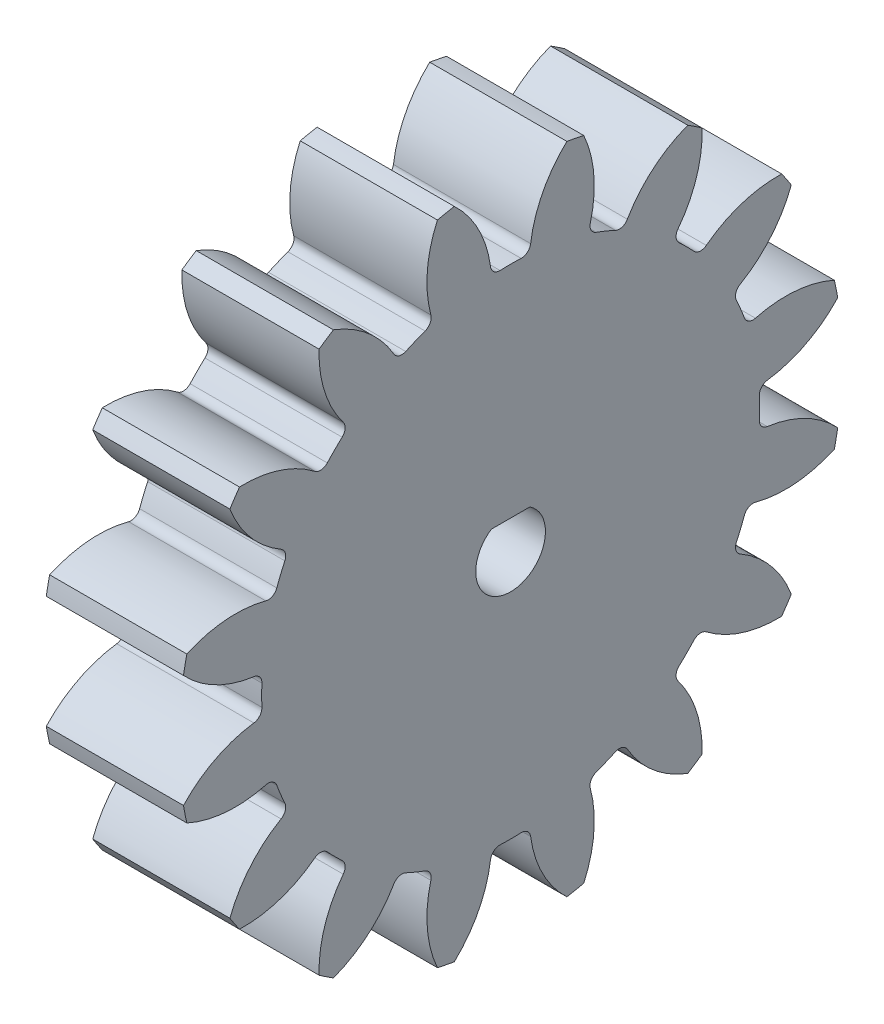
SolidWorks part; units mm, degrees
ref_plane "Plane1" through (0, 0, 0) normal (0, 0, 1) x (1, 0, 0)
ref_plane "Plane2" through (0, 0, 0) normal (0, 1, 0) x (1, 0, 0)
ref_plane "Plane3" through (0, 0, 0) normal (1, 0, 0) x (0, 0, -1)
sketch "HoldingSke" plane through (0, 0, 0) normal (0, 1, 0) x (1, 0, 0)
  line L0 (0, 0) -> (195.3284, -56.0095)
  line L1 (-15, 0) -> (100, 0) construction
  line L2 (0, 0) -> (-2.1039, 2.3779)
  line L3 (0, 0) -> (-11.863, 4.5341)
  line L4 (0, 0) -> (8.3015, 2.3804)
  line L5 (0, 0) -> (-47.5972, -17.7524)
  line L6 (0, 0) -> (-9.7909, -6.6059)
  line L7 (-2.1039, 2.3779) -> (8.8308, 51.9871)
  line L8 (-76.2, 54.61) -> (-75.184, 54.61)
  line L9 (-71.009, 38.7566) -> (-53.1078, 45.2721)
  line L10 (-76.2, 71.12) -> (104.1128, 71.12)
  line L11 (0, 0) -> (-11.811, 0)
  line L12 (-76.2, 101.6) -> (-76.0857, 101.6)
  line L13 (24.9733, 27.94) -> (52.9518, 28.4284)
  line L14 (24.9733, 27.94) -> (24.9746, 27.94)
  line L15 (24.9733, 27.94) -> (100.4006, 29.5858)
  circle A0 centre (0, 0) radius 0.3969
  circle A1 centre (0, 0) radius 21.43
  circle A2 centre (0, 0) radius 38.1
  circle A3 centre (0, 0) radius 0.3969
  dimension "MHD" = 42.86
  dimension "Hub_dia" = 76.2
  dimension "Bore" = 0.7937
  dimension "MBD" = 0.7937
  dimension "Num_teeth" = 16
  dimension "Pitch_radius" = 180.3128
  dimension "Pitch" = 203.2
  dimension "Width" = 11.811
  dimension "Overall_len" = 50.8
  dimension "Show_teeth" = 16
  dimension "Thickness" = 11.811
  dimension "OAL" = 50.8001
  dimension "T_dim" = 1.016
  dimension "Ap" = 20
  dimension "H" = 19.05
  dimension "Backlash" = 0.1143
  dimension "Addendum_fac" = 1
  dimension "Dedendum_fac" = 1.25
  dimension "Clearance_fac" = 0.25
  dimension "Dedendum_add" = 0.0013
sketch "BasProSke" plane through (0, 0, 0) normal (0, 1, 0) x (1, 0, 0)
  line L0 (-10, 0) -> (60, 0) construction
  line L1 (0, 0) -> (0, 28.575)
  line L2 (0, 0) -> (11.811, 0)
  line L3 (11.811, 0) -> (11.811, 28.575)
  line L4 (11.811, 28.575) -> (0, 28.575)
  dimension "Diameter" = 57.15
  dimension "Thickness" = 11.811
revolve "Base-Revolve" add sketch "BasProSke" angle 360 about L0
sketch "TooCutSke" plane through (0, 0, 0) normal (1, 0, 0) x (0, 0, -1)
  line L1 (0, 0) -> (0, 107) construction
  line L2 (0, 0) -> (-2.6895, 25.2572) construction
  line L3 (0, 0) -> (-9.8702, 49.6211) construction
  line L4 (-2.6895, 25.2572) -> (-4.9351, 24.8105) construction
  arc A0 (1.6538, 21.3661) -> (-1.6538, 21.3661) centre (0, 0) ccw
  arc A1 (4.8685, 28.183) -> (-4.8685, 28.183) centre (0, 0) ccw
  circle A2 centre (0, 0) radius 25.4 construction
  circle A3 centre (0, 0) radius 23.8682 construction
  arc A4 (-1.6538, 21.3661) -> (-4.8685, 28.183) centre (-11.7951, 20.7501) ccw
  arc A5 (4.8685, 28.183) -> (1.6538, 21.3661) centre (11.7951, 20.7501) ccw
  dimension "Root_dia" = 42.86
  dimension "Overcut_dia" = 57.2008
  dimension "Pitch_dia" = 50.8
  dimension "Base_dia" = 47.7364
  dimension "Flank_rad" = 10.16
  dimension "Half_ang" = 11.25
  dimension "Half_CT" = 2.2896
extrude "ToothCut" cut sketch "TooCutSke" along normal through all
fillet "Breaks" [suppressed] radius 0.0635 tangent propagation no
fillet "RootFillets" radius 0.795 2 edges at (5.9055, 21.3661, -1.6538) (5.9055, 21.3661, 1.6538)
pattern_circular "TeethCuts" count 16 every 22.5 about axis through (-10, 0, 0) along (1, 0, 0) of "ToothCut", "RootFillets", "Breaks"
sketch "HubNeaOneSke" plane through (0, 0, 0) normal (-1, 0, 0) x (0, 0, 1)
  circle A0 centre (0, 0) radius 21.43
  dimension "Diameter" = 42.86
extrude "HubNearOne" [suppressed] add sketch "HubNeaOneSke" along normal blind 38.9891
sketch "HubNeaBotSke" plane through (0, 0, 0) normal (-1, 0, 0) x (0, 0, 1)
  circle A0 centre (0, 0) radius 21.43
  dimension "Diameter" = 42.86
extrude "HubNearBoth" [suppressed] add sketch "HubNeaBotSke" along normal blind 19.4945
ref_plane "FarPln" through (11.811, 0, 0) normal (1, 0, 0) x (0, 0, -1)
sketch "HubFarSke" plane through (11.811, 0, 0) normal (1, 0, 0) x (0, 0, -1)
  circle A0 centre (0, 0) radius 21.43
  dimension "Diameter" = 42.86
extrude "HubFar" [suppressed] add sketch "HubFarSke" along normal blind 19.4945
sketch "BorSke" plane through (0, 0, 0) normal (1, 0, 0) x (0, 0, -1)
  circle A0 centre (0, 0) radius 0.3969
  dimension "Diameter" = 0.7937
extrude "Bore" cut sketch "BorSke" along normal mid plane 101.6001
sketch "KeySke" plane through (0, 0, 0) normal (1, 0, 0) x (0, 0, -1)
  line L0 (-0.127, 0) -> (-0.127, 0.6191)
  line L1 (-0.127, 0.6191) -> (0.127, 0.6191)
  line L2 (0.127, 0.6191) -> (0.127, 0)
  line L3 (0, 0) -> (0, 34) construction
  line L4 (-0.127, 0) -> (0.127, 0)
  dimension "Offset" = 0.6191
  dimension "Width" = 0.254
extrude "Keyway" [suppressed] cut sketch "KeySke" along normal mid plane 101.6001
pattern_circular "Keyway2" [suppressed] count 2 every 90 about axis through (-10, 0, 0) along (1, 0, 0)
sketch "Sketch1" plane through (11.811, 0, 0) normal (1, 0, 0) x (0, 0, -1)
  line L0 (-1.6583, 2.5) -> (1.6583, 2.5)
  arc A0 (-1.6583, 2.5) -> (1.6583, 2.5) centre (0, 0) ccw
  dimension "D1" = 6
  dimension "D2" = 2.5
extrude "Cut-Extrude1" cut sketch "Sketch1" against normal through all
equation "' \"Pitch@HoldingSke\" = 4"
equation "' \"Num_teeth@HoldingSke\" = 12"
equation "' \"Ap@HoldingSke\" =  20"
equation "' \"Width@HoldingSke\" = 0.5"
equation "' \"Hub_dia@HoldingSke\"= 1"
equation "' \"Overall_len@HoldingSke\" = 1.0"
equation "' \"Bore@HoldingSke\" = 0.75"
equation "' \"T_dim@HoldingSke\" = 0.85"
equation "' \"Width@KeySke\" = 0.25"
equation "' \"Show_teeth@HoldingSke\" = 13"
equation "' \"Backlash@HoldingSke\" = 0.009"
equation "' \"Addendum_fac@HoldingSke\" = 1.0"
equation "' \"Dedendum_fac@HoldingSke\" = 1.25"
equation "' \"Dedendum_add@HoldingSke\" = 0.00005"
equation "' \"Clearance_fac@HoldingSke\" = 0.25"
equation "' \"Pitch@HoldingSke\" = 0.5"
equation "' \"Num_teeth@HoldingSke\" = 23"
equation "' \"Show_teeth@HoldingSke\" = 23"
equation "' \"Backlash@HoldingSke\" = 0.0375"
equation "\"Overcut_dia@TooCutSke\" = (\"Num_teeth@HoldingSke\" + 2 * \"Addendum_fac@HoldingSke\") / \"Pitch@HoldingSke\" + 0.002"
equation "\"Pitch_dia@TooCutSke\" = \"Num_teeth@HoldingSke\" / \"Pitch@HoldingSke\""
equation "\"Base_dia@TooCutSke\" = \"Num_teeth@HoldingSke\" / \"Pitch@HoldingSke\" * cos((\"Ap@HoldingSke\"  * 3.14159265 / 180))"
equation "\"Root_dia@TooCutSke\" = (\"Num_teeth@HoldingSke\" + 2) / \"Pitch@HoldingSke\" - 2 * (\"Addendum_fac@HoldingSke\" + \"Dedendum_fac@HoldingSke\") / \"Pitch@HoldingSke\" - \"Dedendum_add@HoldingSke\" * 2"
equation "\"Half_ang@TooCutSke\" = 180 / \"Num_teeth@HoldingSke\""
equation "\"Half_CT@TooCutSke\" = \"Num_teeth@HoldingSke\" / \"Pitch@HoldingSke\" * sin((3.14159265 / 2 / \"Num_teeth@HoldingSke\")) / 2 - 7 * \"Backlash@HoldingSke\" / 4"
equation "\"Flank_rad@TooCutSke\" = \"Num_teeth@HoldingSke\" / \"Pitch@HoldingSke\" / 5"
equation "\"Radius@RootFillets\" = \"Clearance_fac@HoldingSke\" / \"Pitch@HoldingSke\" + \"Dedendum_add@HoldingSke\""
equation "\"Break_rad@Breaks\" = 0.02 / \"Pitch@HoldingSke\""
equation "\"Thickness@HoldingSke\" = \"Width@HoldingSke\""
equation "\"OAL@HoldingSke\" = \"Thickness@HoldingSke\""
equation "\"MHD@HoldingSke\" = (\"Num_teeth@HoldingSke\" + 2) / \"Pitch@HoldingSke\" - 2 * (\"Addendum_fac@HoldingSke\" + \"Dedendum_fac@HoldingSke\")  / \"Pitch@HoldingSke\" - \"Dedendum_add@HoldingSke\" * 2"
equation "\"MBD@HoldingSke\" = (\"Num_teeth@HoldingSke\" + 2) / \"Pitch@HoldingSke\" - 2 * (\"Addendum_fac@HoldingSke\" + \"Dedendum_fac@HoldingSke\")  / \"Pitch@HoldingSke\" - \"Dedendum_add@HoldingSke\" * 2 - 0.002"
equation "\"MHD@HoldingSke\" = ((sgn( \"MHD@HoldingSke\" - \"Hub_dia@HoldingSke\" )-1)*( \"MHD@HoldingSke\" - \"Hub_dia@HoldingSke\" ))/-2+ \"Hub_dia@HoldingSke\""
equation "\"MBD@HoldingSke\" = ((sgn( \"MBD@HoldingSke\" - \"Bore@HoldingSke\" )-1)*( \"MBD@HoldingSke\" - \"Bore@HoldingSke\" ))/-2+ \"Bore@HoldingSke\""
equation "\"OAL@HoldingSke\" = ((sgn( \"OAL@HoldingSke\" - \"Overall_len@HoldingSke\" )+1)*( \"OAL@HoldingSke\" - \"Overall_len@HoldingSke\" ))/2 + \"Overall_len@HoldingSke\" + 0.000002"
equation "\"Num_teeth@TeethCuts\" = int( \"Show_teeth@HoldingSke\" ) + 1"
equation "\"Num_teeth@TeethCuts\" = ((sgn( \"Num_teeth@TeethCuts\" - \"Num_teeth@HoldingSke\" )-1)*( \"Num_teeth@TeethCuts\" - \"Num_teeth@HoldingSke\" ))/-2+ \"Num_teeth@HoldingSke\""
equation "\"Num_teeth@TeethCuts\" = ((sgn( \"Num_teeth@TeethCuts\" - 2.0)+1)*( \"Num_teeth@TeethCuts\" - 2.0))/2 +2.0"
equation "\"Angle@TeethCuts\" = 360.0 / \"Num_teeth@HoldingSke\""
equation "\"Diameter@BasProSke\" = (\"Num_teeth@HoldingSke\" + 2 * \"Addendum_fac@HoldingSke\") / \"Pitch@HoldingSke\""
equation "\"Thickness@BasProSke\"  = \"Thickness@HoldingSke\""
equation "' \"Fillet_rad@BasProSke\" =  \"Thickness@HoldingSke\" * 0.05"
equation "\"MHD@HoldingSke\" = ((sgn( \"MHD@HoldingSke\" - \"Root_dia@TooCutSke\" )-1)*( \"MHD@HoldingSke\" - \"Root_dia@TooCutSke\" ))/-2+ \"Root_dia@TooCutSke\""
equation "\"Diameter@HubNeaOneSke\" = \"MHD@HoldingSke\""
equation "\"Length@HubNearOne\" = \"OAL@HoldingSke\" - \"Thickness@BasProSke\""
equation "\"Diameter@HubNeaBotSke\" = \"MHD@HoldingSke\""
equation "\"Length@HubNearBoth\" = ( \"OAL@HoldingSke\" - \"Thickness@BasProSke\" ) / 2.0"
equation "\"Thickness@FarPln\" = \"Thickness@BasProSke\""
equation "\"Diameter@HubFarSke\" = \"MHD@HoldingSke\""
equation "\"Length@HubFar\" = ( \"OAL@HoldingSke\" - \"Thickness@BasProSke\" ) / 2.0"
equation "\"Diameter@BorSke\" = \"MBD@HoldingSke\""
equation "\"D1@Bore\" = \"OAL@HoldingSke\" * 2.0"
equation "\"D1@Keyway\" = \"OAL@HoldingSke\" * 2.0"
equation "\"Offset@KeySke\" = \"T_dim@HoldingSke\" - \"MBD@HoldingSke\" / 2.0"
